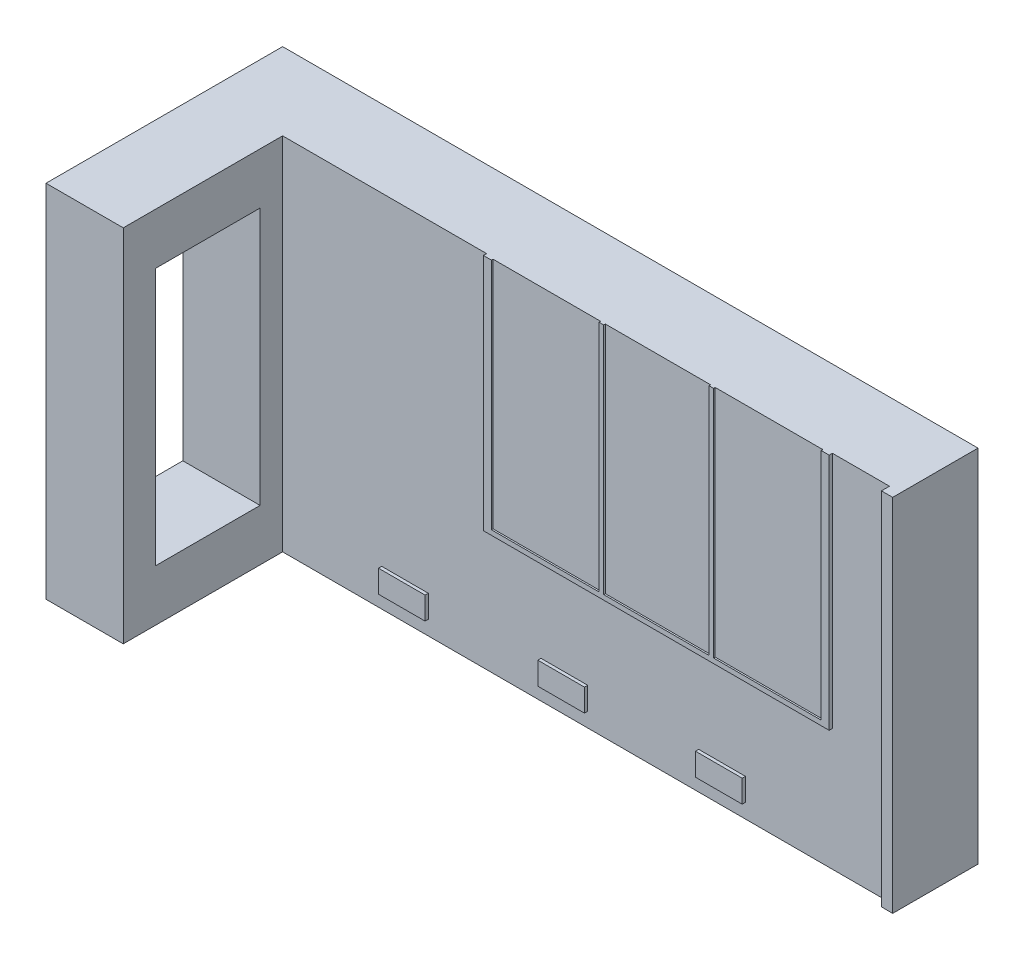
SolidWorks part; units mm, degrees
ref_plane "Front Plane" through (0, 0, 0) normal (0, 0, 1) x (1, 0, 0)
ref_plane "Top Plane" through (0, 0, 0) normal (0, 1, 0) x (1, 0, 0)
ref_plane "Right Plane" through (0, 0, 0) normal (1, 0, 0) x (0, 0, -1)
sketch "Wall Footprint" plane through (0, 0, 0) normal (0, 1, 0) x (1, 0, 0)
  line L0 (-205.7116, 250.3406) -> (4671.0884, 250.3406)
  line L1 (4671.0884, 250.3406) -> (4671.0884, 859.9406)
  line L2 (4671.0884, 859.9406) -> (-815.3116, 859.9406)
  line L3 (-815.3116, 859.9406) -> (-815.3116, -1006.9594)
  line L4 (-815.3116, -1006.9594) -> (-205.7116, -1006.9594)
  line L5 (-205.7116, -1006.9594) -> (-205.7116, 250.3406)
  dimension "D1" = 4876.8
  dimension "D2" = 609.6
  dimension "D3" = 1257.3
  dimension "D4" = 609.6
  dimension "D5" = 609.6
extrude "House Extrude +Y" add sketch "Wall Footprint" along normal blind 2842.753
sketch "Vents" plane through (0, 0, -250.3406) normal (0, 0, 1) x (1, 0, 0)
  line L0 (-205.7116, 0) -> (4671.0884, 0) construction
  line L1 (3077.2384, 292.1) -> (3445.5384, 292.1)
  line L2 (3077.2384, 292.1) -> (3077.2384, 114.3)
  line L3 (3077.2384, 114.3) -> (3445.5384, 114.3)
  line L4 (3445.5384, 292.1) -> (3445.5384, 114.3)
  line L5 (2200.9384, 292.1) -> (1832.6384, 292.1)
  line L6 (2200.9384, 292.1) -> (2200.9384, 114.3)
  line L7 (2200.9384, 114.3) -> (1832.6384, 114.3)
  line L8 (1832.6384, 292.1) -> (1832.6384, 114.3)
  line L10 (1485.5537, 406.4) -> (51485.5537, 406.4) construction
  line L11 (-205.7116, 2842.753) -> (-205.7116, 0) construction
  line L12 (575.3384, 292.1) -> (943.6384, 292.1)
  line L13 (575.3384, 292.1) -> (575.3384, 114.3)
  line L14 (575.3384, 114.3) -> (943.6384, 114.3)
  line L15 (943.6384, 292.1) -> (943.6384, 114.3)
  line L16 (4671.0884, 2842.753) -> (4671.0884, 0) construction
  dimension "D1" = 114.3
  dimension "D2" = 368.3
  dimension "D3" = 177.8
  dimension "D4" = 876.3
  dimension "D5" = 1225.55
  dimension "D6" = 406.4
  dimension "D7" = 781.05
  dimension "D8" = 114.3
sketch "Door" plane through (-205.7116, 0, 0) normal (1, 0, 0) x (0, 0, -1)
  line L1 (-752.9594, 2438.4) -> (72.5406, 2438.4)
  line L2 (-752.9594, 2438.4) -> (-752.9594, 406.4)
  line L3 (-752.9594, 406.4) -> (72.5406, 406.4)
  line L4 (72.5406, 2438.4) -> (72.5406, 406.4)
  line L5 (250.3406, 2842.753) -> (250.3406, 0) construction
  line L6 (-1006.9594, 0) -> (250.3406, 0) construction
  dimension "D1" = 825.5
  dimension "D2" = 177.8
  dimension "D3" = 406.4
  dimension "D4" = 2032
extrude "Door Cut -X" cut sketch "Door" against normal up to surface (609.6 mm away) up to face at (-815.3116, 1421.3765, 73.5094)
sketch "Window" plane through (0, 0, -250.3406) normal (0, 0, 1) x (1, 0, 0)
  line L0 (-205.7116, 2842.753) -> (4671.0884, 2842.753) construction
  line L1 (1403.4386, 962.116) -> (4131.8947, 962.116)
  line L2 (1403.4386, 962.116) -> (1403.4386, 2842.753)
  line L3 (1403.4386, 2842.753) -> (4131.8947, 2842.753)
  line L4 (4131.8947, 962.116) -> (4131.8947, 2842.753)
  line L5 (1466.9386, 2842.753) -> (1466.9386, 1000.216)
  line L6 (898.1983, 635) -> (50898.1983, 635) construction
  line L7 (-205.7116, 0) -> (4671.0884, 0) construction
  line L8 (-205.7116, 2842.753) -> (-205.7116, 0) construction
  line L9 (1466.9386, 1000.216) -> (4068.3947, 1000.216)
  line L10 (4068.3947, 1000.216) -> (4068.3947, 2842.753)
  line L12 (2315.0407, 2842.753) -> (2353.1407, 2842.753)
  line L13 (2315.0407, 2842.753) -> (2315.0407, 1000.216)
  line L14 (2315.0407, 1000.216) -> (2353.1407, 1000.216)
  line L15 (2353.1407, 2842.753) -> (2353.1407, 1000.216)
  line L16 (3220.2927, 1000.216) -> (3182.1927, 1000.216)
  line L17 (3220.2927, 1000.216) -> (3220.2927, 2842.753)
  line L18 (3220.2927, 2842.753) -> (3182.1927, 2842.753)
  line L19 (3182.1927, 1000.216) -> (3182.1927, 2842.753)
  line M7 (4671.0884, 2842.753) -> (-205.7116, 2842.753)
  dimension "D1" = 635
  dimension "D2" = 327.116
  dimension "D3" = 1609.1502
  dimension "D4" = 2728.4561
  dimension "D5" = 63.5
  dimension "D6" = 38.1
  dimension "D7" = 63.5
  dimension "D8" = 848.102
  dimension "D10" = 38.1
  dimension "D9" = 38.1
  dimension "D11" = 848.102
extrude "Window Frame Extrude +Z" add sketch "Window" along normal blind 25.4 contours L10 L9 L5 L3 L2 L1 L4 M7 | L15 L14 L13 L12 | L17 L18 L19 L16 region at (1436.5766, 1902.4345, -250.3406)
extrude "Window Glass Extrude +Z" add sketch "Window<3>" along normal blind 12.7 contours L13 L3 L5 L9 | L9 L19 L3 L15 | L17 L9 L10 L3 region at (1890.9896, 1921.4845, -250.3406) region at (3644.3437, 1921.4845, -250.3406) region at (2767.6667, 1921.4845, -250.3406)
sketch "Window<3>" plane through (0, 0, -250.3406) normal (0, 0, 1) x (1, 0, 0) same geometry as "Window"
sketch "Drain Pipe" plane through (0, 0, -250.3406) normal (0, 0, 1) x (1, 0, 0)
  line L0 (4131.8947, 2842.753) -> (4671.0884, 2842.753) construction
  line L1 (4582.1884, 2842.753) -> (4671.0884, 2842.753)
  line L2 (4582.1884, 2842.753) -> (4582.1884, 0)
  line L3 (4582.1884, 0) -> (4671.0884, 0)
  line L4 (4671.0884, 2842.753) -> (4671.0884, 0)
  dimension "D1" = 88.9
extrude "Drain Pipe Extrude +Z" add sketch "Drain Pipe" along normal blind 63.5
extrude "Vents Extrude +Z" add sketch "Vents" along normal blind 25.4
equation "\"deckHeight\"= 16'Height to the top of the deck"
equation "\"D8@Window\" =  ( \"D4@Window\" - \"D5@Window\" - \"D7@Window\" )  / 3 - 1.5 / 2"
